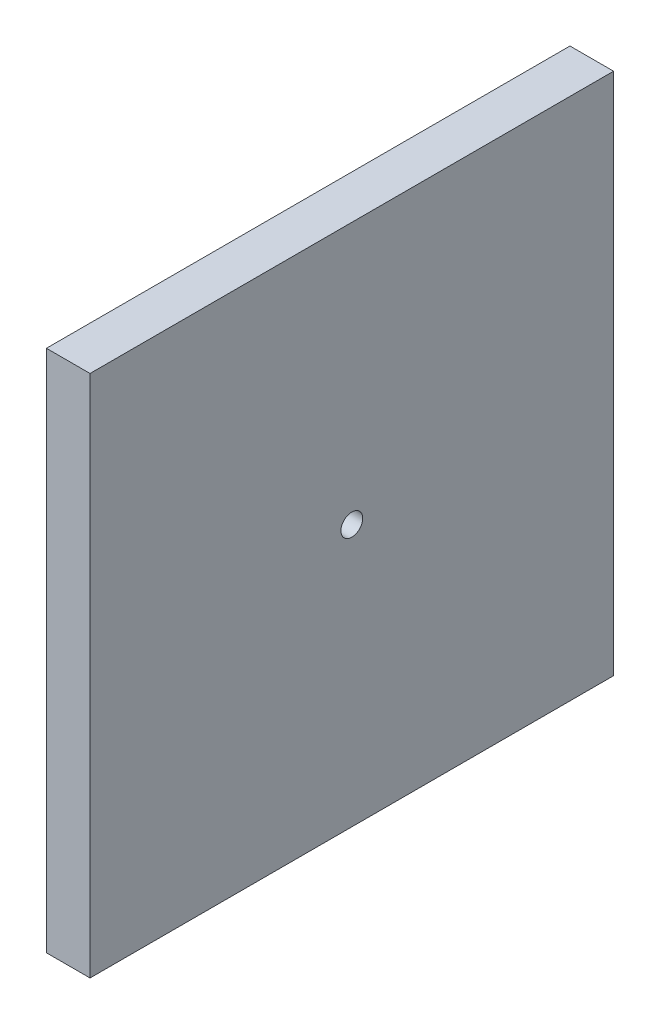
SolidWorks part; units mm, degrees
ref_plane "Front Plane" through (0, 0, 0) normal (0, 0, 1) x (1, 0, 0)
ref_plane "Top Plane" through (0, 0, 0) normal (0, 1, 0) x (1, 0, 0)
ref_plane "Right Plane" through (0, 0, 0) normal (1, 0, 0) x (0, 0, -1)
sketch "Sketch1" plane through (0, 0, 0) normal (1, 0, 0) x (0, 0, -1)
  line L1 (-152.4, -152.4) -> (152.4, -152.4)
  line L2 (-152.4, -152.4) -> (-152.4, 152.4)
  line L3 (-152.4, 152.4) -> (152.4, 152.4)
  line L4 (152.4, -152.4) -> (152.4, 152.4)
  line L5 (-152.4, -152.4) -> (152.4, 152.4) construction
  line L6 (-152.4, 152.4) -> (152.4, -152.4) construction
  point P0 (0, 0)
  dimension "D1" = 304.8
  dimension "D2" = 304.8
extrude "Boss-Extrude1" add sketch "Sketch1" along normal mid plane 25.4
ref_axis "Axis1" through (13.97, 0, 0) along (-1, 0, 0)
sketch "Sketch2" plane through (0, 0, 0) normal (1, 0, 0) x (0, 0, -1)
  circle A0 centre (0, 0) radius 6.35
  dimension "D1" = 12.7
extrude "Cut-Extrude1" cut sketch "Sketch2" against normal through all both and the other way through all
